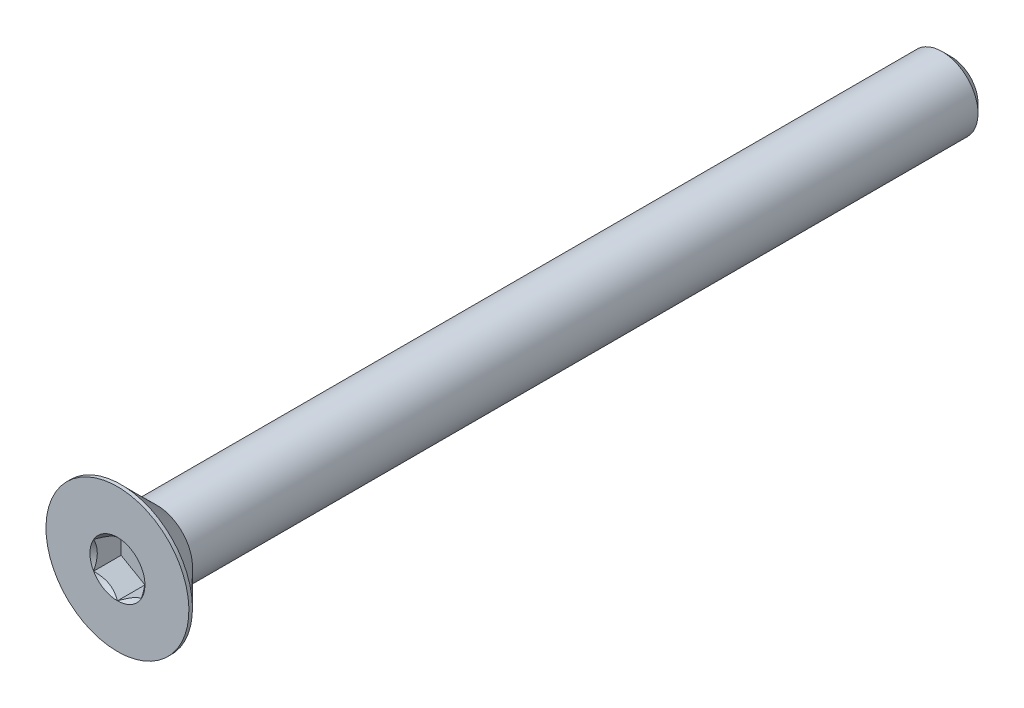
SolidWorks part; units mm, degrees
material "AISI 304"
ref_plane "Front" through (0, 0, 0) normal (0, 0, 1) x (1, 0, 0)
ref_plane "Top" through (0, 0, 0) normal (0, 1, 0) x (1, 0, 0)
ref_plane "Right" through (0, 0, 0) normal (1, 0, 0) x (0, 0, -1)
sketch "Sketch1" plane through (0, 0, 0) normal (1, 0, 0) x (0, 0, -1)
  line L0 (0, 6) -> (0.3, 6) construction
  line L1 (0.3, 6) -> (3.3, 3) construction
  line L2 (0, 3) -> (70, 3)
  line L3 (70, 3) -> (70, 0)
  line L4 (70, 0) -> (0, 0)
  line L5 (0, 0) -> (0, 6) construction
  line L6 (0, 6) -> (0, -6) construction
  line L7 (70, 3) -> (70, -3) construction
  line L8 (0, -6) -> (0.3, -6) construction
  line L9 (0.3, -6) -> (3.3, -3) construction
  line L11 (0, 3) -> (0, 0)
  line L12 (3.3, 3) -> (3.3, 0) construction
revolve "Revolve1" add sketch "Sketch1" angle 360 mid plane about L4
sketch "Sketch3" plane through (0, 0, -70) normal (0, 0, -1) x (-1, 0, 0)
  circle A0 centre (0, 0) radius 3
curve "Helix/Spiral1" pitch 1 height 70 turns 70
sketch "Sketch2" plane through (0, 0, 0) normal (1, 0, 0) x (0, 0, -1)
  line L0 (70, 3) -> (70.875, 3)
  line L1 (70.875, 3) -> (70.5, 2.3505)
  line L2 (70.5, 2.3505) -> (70.375, 2.3505)
  line L3 (70.375, 2.3505) -> (70, 3)
  line L4 (70.1875, 2.6752) -> (70.6875, 2.6752) construction
  dimension "D1" = 60
  dimension "D2" = 0.125
  dimension "D3" = 0.5
chamfer "Chamfer1" distance 0.75 angle 45 1 edges at (0, 3, -70)
sweep "Cut-Sweep1" [suppressed] cut profiles "Sketch2" path "Helix/Spiral1"
sketch "Sketch7" plane through (0, 0, 0) normal (1, 0, 0) x (0, 0, -1)
  line L0 (0, 6) -> (0.3, 6) construction
  line L1 (0.3, 6) -> (3.3, 3) construction
  line L2 (0, 6) -> (0.3, 6)
  line L3 (0.3, 6) -> (3.3, 3)
  line L4 (3.3, 3) -> (3.3, 0) construction
  line L5 (3.3, 3) -> (3.3, 0)
  line L7 (0, 0) -> (0, 6) construction
  line L8 (0, 0) -> (0, 6)
  line L9 (0, 0) -> (3.3, 0)
  line L10 (6.6, 0) -> (-6.6, 0) construction
revolve "Revolve2" add sketch "Sketch7" angle 360 mid plane about L9
ref_plane "Plane1" through (0, 0, -3.3) normal (0, 0, 1) x (1, 0, 0)
sketch "Sketch8" plane through (0, 0, -3.3) normal (0, 0, 1) x (1, 0, 0)
  circle A0 centre (0, 0) radius 3
extrude "Boss-Extrude1" add sketch "Sketch8" against normal through all draft 45
sketch "Sketch5" plane through (0, 0, 0) normal (0, 0, 1) x (1, 0, 0)
  line L1 (2, -1.1547) -> (2, 1.1547)
  line L2 (2, 1.1547) -> (0, 2.3094)
  line L3 (0, 2.3094) -> (-2, 1.1547)
  line L4 (-2, 1.1547) -> (-2, -1.1547)
  line L5 (-2, -1.1547) -> (0, -2.3094)
  line L6 (0, -2.3094) -> (2, -1.1547)
  circle A0 centre (0, 0) radius 2 construction
  dimension "Hex" = 4
extrude "Cut-Extrude2" cut sketch "Sketch5" against normal blind 2.31
sketch "Sketch6" plane through (0, 0, 0) normal (0, 0, 1) x (1, 0, 0)
  circle A0 centre (0, 0) radius 2.3094
extrude "Cut-Extrude3" cut sketch "Sketch6" against normal blind 2.31 draft 45
sketch "Sketch9" [suppressed] plane through (0, 0, -5.5) normal (0, 0, 1) x (1, 0, 0)
  circle A1 centre (0, 0) radius 5
  circle A2 centre (0, 0) radius 5
  point P0 (0, 5)
  dimension "D1" = 0
extrude "Boss-Extrude2" [suppressed] add sketch "Sketch9" against normal offset from surface (18.5 mm away) 26
fillet "Fillet1" [suppressed] radius 0.6
sketch "Sketch10" plane through (0, 0, 0) normal (1, 0, 0) x (0, 0, -1)
  line L0 (70, 3) -> (70, -3) construction
  point P0 (68.5, -3)
  dimension "D1" = 1.5
equation "\"D3@Helix/Spiral1\" = \"Lg@Sketch1\""
equation "\"D2@Sketch2\" = \"D4@Helix/Spiral1\" * .125"
equation "\"D3@Sketch2\" = \"D4@Helix/Spiral1\" * .5"
equation "\"D1@Chamfer1\" = \"D4@Helix/Spiral1\" * .75"
equation "\"D1@Cut-Extrude2\" = \"Head Ht@Sketch1\" * .7"
equation "\"D1@Sketch10\" = \"D4@Helix/Spiral1\" * 1.5"
equation "\"D1@Cut-Extrude3\" = \"D1@Cut-Extrude2\""
equation "\"D1@Fillet1\" = \"Dia@Sketch1\" * .1"
